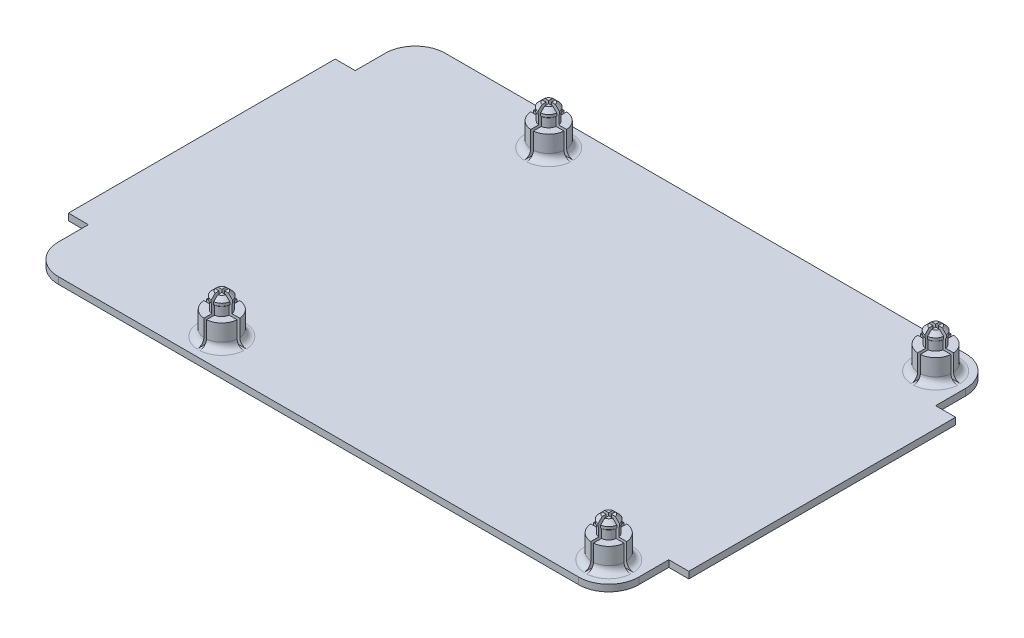
SolidWorks part; units mm, degrees
ref_plane "Front Plane" through (0, 0, 0) normal (0, 0, 1) x (1, 0, 0)
ref_plane "Top Plane" through (0, 0, 0) normal (0, 1, 0) x (1, 0, 0)
ref_plane "Right Plane" through (0, 0, 0) normal (1, 0, 0) x (0, 0, -1)
sketch "Sketch1" plane through (0, 0, 0) normal (0, 1, 0) x (1, 0, 0)
  line L1 (43.5, -29) -> (-43.5, -29)
  line L2 (43.5, -29) -> (43.5, 29)
  line L3 (43.5, 29) -> (-43.5, 29)
  line L4 (-43.5, -29) -> (-43.5, 29)
  line L5 (43.5, -29) -> (-43.5, 29) construction
  line L6 (43.5, 29) -> (-43.5, -29) construction
  point P0 (0, 0)
  dimension "D1" = 87
  dimension "D2" = 58
extrude "Boss-Extrude1" add sketch "Sketch1" along normal blind 1
sketch "Sketch2" plane through (0, 1, 0) normal (0, 1, 0) x (1, 0, 0)
  line L0 (43.5, -29) -> (43.5, 29) construction
  line L1 (39, -24.5) -> (-19, -24.5) construction
  line L2 (39, -24.5) -> (39, 24.5) construction
  line L3 (39, 24.5) -> (-19, 24.5) construction
  line L4 (-19, -24.5) -> (-19, 24.5) construction
  line L5 (39, -24.5) -> (-19, 24.5) construction
  line L6 (39, 24.5) -> (-19, -24.5) construction
  circle A0 centre (-19, 24.5) radius 2.5
  circle A1 centre (39, 24.5) radius 2.5
  circle A2 centre (39, -24.5) radius 2.5
  circle A3 centre (-19, -24.5) radius 2.5
  point P0 (10, 0)
  dimension "D4" = 5
  dimension "D1" = 58
  dimension "D2" = 49
  dimension "D3" = 4.5
extrude "Boss-Extrude2" add sketch "Sketch2" along normal blind 3.5
sketch "Sketch3" plane through (0, 4.5, 0) normal (0, 1, 0) x (1, 0, 0)
  circle A0 centre (-19, 24.5) radius 1.325
  circle A1 centre (39, 24.5) radius 1.325
  circle A2 centre (39, -24.5) radius 1.325
  circle A3 centre (-19, -24.5) radius 1.325
  dimension "D1" = 2.65
extrude "Boss-Extrude3" add sketch "Sketch3" along normal blind 1.4
sketch "Sketch4" plane through (0, 5.9, 0) normal (0, 1, 0) x (1, 0, 0)
  circle A0 centre (-19, 24.5) radius 1.425
  circle A1 centre (39, 24.5) radius 1.425
  circle A2 centre (39, -24.5) radius 1.425
  circle A3 centre (-19, -24.5) radius 1.425
  circle A4 centre (-19, 24.5) radius 1.325 construction
  dimension "D1" = 0.1
extrude "Boss-Extrude4" add sketch "Sketch4" along normal blind 1
chamfer "Chamfer2" distance 0.1 angle 45 4 edges at (39, 5.9, 25.825) (39, 5.9, -23.175) (-19, 5.9, -23.175) (-19, 5.9, 25.825)
chamfer "Chamfer1" distance 0.6 angle 45 4 edges at (39, 6.9, -23.075) (39, 6.9, 25.925) (-19, 6.9, 25.925) (-19, 6.9, -23.075)
sketch "Sketch5" plane through (0, 6.9, 0) normal (0, 1, 0) x (1, 0, 0)
  line L0 (-21.5, 24.5) -> (41.5, 24.5) construction
  line L1 (-21.5, -24.5) -> (41.5, -24.5) construction
  line L2 (39, -27) -> (39, 27) construction
  line L3 (-19, 27) -> (-19, -27) construction
  line L4 (-21.5, 24.3) -> (41.5, 24.3)
  line L5 (-19.2, 27) -> (-19.2, -27)
  line L6 (-21.5, -24.7) -> (41.5, -24.7)
  line L7 (39.2, -27) -> (39.2, 27)
  line L8 (-21.5, 24.7) -> (41.5, 24.7)
  line L9 (-18.8, 27) -> (-18.8, -27)
  line L10 (-21.5, -24.3) -> (41.5, -24.3)
  line L11 (38.8, -27) -> (38.8, 27)
  line L12 (-21.5, 24.7) -> (-21.5, 24.3)
  line L13 (-19.2, 27) -> (-18.8, 27)
  line L14 (38.8, 27) -> (39.2, 27)
  line L15 (41.5, 24.7) -> (41.5, 24.3)
  line L16 (41.5, -24.3) -> (41.5, -24.7)
  line L17 (39.2, -27) -> (38.8, -27)
  line L18 (-21.5, -24.3) -> (-21.5, -24.7)
  line L19 (-19.2, -27) -> (-18.8, -27)
  circle A0 centre (-19, 24.5) radius 2.5 construction
  circle A1 centre (39, 24.5) radius 2.5 construction
  circle A2 centre (-19, -24.5) radius 2.5 construction
  circle A3 centre (-19, -24.5) radius 2.5 construction
  circle A4 centre (39, -24.5) radius 2.5 construction
  circle A5 centre (39, -24.5) radius 2.5 construction
  circle A6 centre (39, 24.5) radius 2.5 construction
  circle A7 centre (-19, 24.5) radius 2.5 construction
  dimension "D1" = 0.2
  dimension "D2" = 0.2
extrude "Cut-Extrude1" cut sketch "Sketch5" against normal up to surface (5.9 mm away) contours L9 L19 L5 L13 | L8 L15 L4 L12 | L11 L14 L7 L17 | L10 L16 L6 L18 up to face at (-19, 1, 27)
fillet "Fillet2" radius 1 16 edges at (-17.2322, 1, 26.2678) (-20.7678, 1, 26.2678) (-17.2322, 1, 22.7322) (-20.7678, 1, 22.7322) (40.7678, 1, 26.2678) (37.2322, 1, 26.2678) (40.7678, 1, 22.7322) (37.2322, 1, 22.7322) (40.7678, 1, -22.7322) (37.2322, 1, -22.7322) (40.7678, 1, -26.2678) (37.2322, 1, -26.2678) (-17.2322, 1, -26.2678) (-20.7678, 1, -26.2678) (-17.2322, 1, -22.7322) (-20.7678, 1, -22.7322)
fillet "Fillet3" radius 4.5 4 edges at (-43.5, 0.5, 29) (-43.5, 0.5, -29) (43.5, 0.5, -29) (43.5, 0.5, 29)
sketch "Sketch6" plane through (0, 0, 0) normal (0, -1, 0) x (1, 0, 0)
  line L0 (-43.5, -24.5) -> (-43.5, 24.5) construction
  line L1 (46.5, -20) -> (-46.5, -20)
  line L2 (46.5, -20) -> (46.5, 20)
  line L3 (46.5, 20) -> (-46.5, 20)
  line L4 (-46.5, -20) -> (-46.5, 20)
  line L5 (46.5, -20) -> (-46.5, 20) construction
  line L6 (46.5, 20) -> (-46.5, -20) construction
  point P0 (0, 0)
  dimension "D1" = 40
  dimension "D2" = 3
extrude "Boss-Extrude5" add sketch "Sketch6" against normal up to surface (1 mm away) up to face at (-20.5073, 1, 22.9927)
